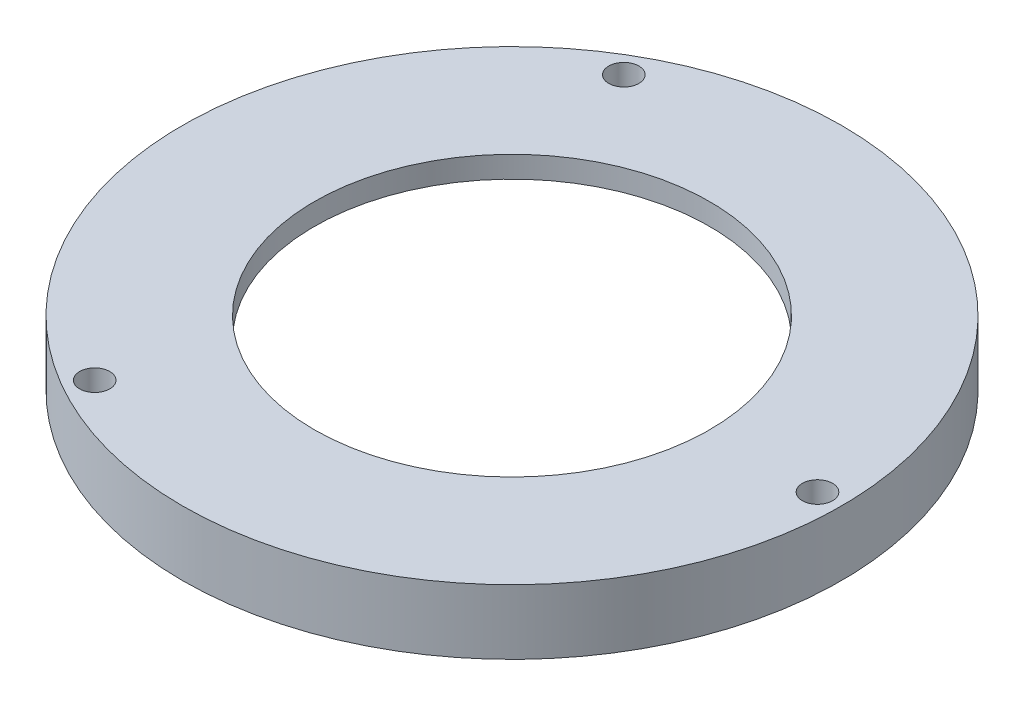
SolidWorks part; units mm, degrees
ref_plane "Front Plane" through (0, 0, 0) normal (0, 0, 1) x (1, 0, 0)
ref_plane "Top Plane" through (0, 0, 0) normal (0, 1, 0) x (1, 0, 0)
ref_plane "Right Plane" through (0, 0, 0) normal (1, 0, 0) x (0, 0, -1)
sketch "Sketch1" plane through (0, 0, 0) normal (0, 1, 0) x (1, 0, 0)
  line L0 (0, 0) -> (42.5, 0) construction
  circle A0 centre (0, 0) radius 45.85
  circle A1 centre (0, 0) radius 27.5
  circle A2 centre (42.5, 0) radius 2.1
  circle A3 centre (-21.25, -36.8061) radius 2.1
  circle A4 centre (-21.25, 36.8061) radius 2.1
  circle A5 centre (0, 0) radius 39.3
  point P13 (0, 0)
  dimension "D1" = 91.7
  dimension "D2" = 55
  dimension "D4" = 4.2
  dimension "D6" = 78.6
  dimension "D3" = 42.5
  dimension "D5" = 3
extrude "Boss-Extrude1" add sketch "Sketch1" against normal blind 6 contours A0 A5 A2 A4 A3 region at (-44.5532, 0, 0)
extrude "Boss-Extrude2" add sketch "Sketch1<4>" along normal blind 3 contours A1 A5 | A0 A5 A2 A4 A3 region at (-44.5532, 0, 0) region at (-38.1884, 0, 0)
sketch "Sketch1<4>" plane through (0, 0, 0) normal (0, 1, 0) x (1, 0, 0) same geometry as "Sketch1"
equation "\"bearing_21_OD\"= 21mm"
equation "\"pin_cirlce_diameter\"= 75mm"
equation "\"pin_diam\"= 6mm"
equation "\"gear_thickness\"= 4mm"
equation "\"ball_bearing_diam\"= 2.96mm"
equation "\"bearing_21_outer_clearance\"= 0mm'change this"
equation "\"bearing_15_OD\"= 15mm"
equation "\"bearing_15_outer_clearance\"= 0mm'change this"
equation "\"thrust_bearing_thickness\"= 5mm'measure this irl and change"
equation "\"D1@Boss-Extrude1\"=\"thrust_bearing_thickness\"+1mm"
